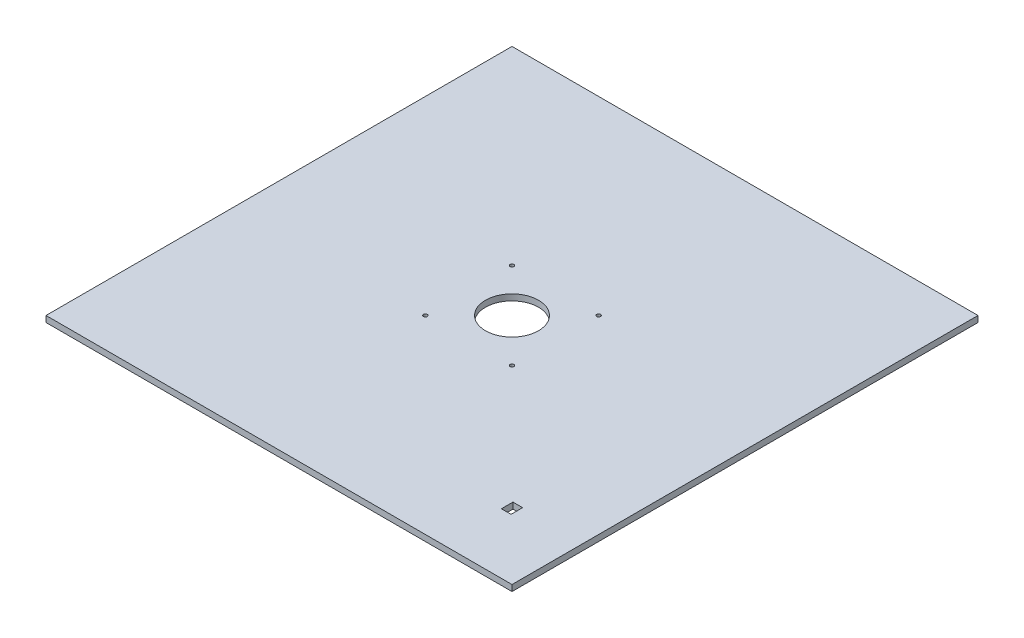
SolidWorks part; units mm, degrees
ref_plane "Front Plane" through (0, 0, 0) normal (0, 0, 1) x (1, 0, 0)
ref_plane "Top Plane" through (0, 0, 0) normal (0, 1, 0) x (1, 0, 0)
ref_plane "Right Plane" through (0, 0, 0) normal (1, 0, 0) x (0, 0, -1)
sketch "Sketch1" plane through (0, 0, 0) normal (0, 1, 0) x (1, 0, 0)
  line L1 (-241.3, -241.3) -> (241.3, -241.3)
  line L2 (-241.3, -241.3) -> (-241.3, 241.3)
  line L3 (-241.3, 241.3) -> (241.3, 241.3)
  line L4 (241.3, -241.3) -> (241.3, 241.3)
  line L5 (-241.3, -241.3) -> (241.3, 241.3) construction
  line L6 (-241.3, 241.3) -> (241.3, -241.3) construction
  point P0 (0, 0)
  dimension "D1" = 482.6
  dimension "D2" = 482.6
extrude "Boss-Extrude1" add sketch "Sketch1" along normal blind 6.35
sketch "Sketch2" plane through (0, 6.35, 0) normal (0, 1, 0) x (1, 0, 0)
  line L1 (-44.8437, -44.8437) -> (44.8437, -44.8437) construction
  line L2 (-44.8437, -44.8437) -> (-44.8437, 44.8437) construction
  line L3 (-44.8437, 44.8437) -> (44.8437, 44.8437) construction
  line L4 (44.8437, -44.8437) -> (44.8437, 44.8437) construction
  line L5 (-44.8437, -44.8437) -> (44.8437, 44.8437) construction
  line L6 (-44.8437, 44.8437) -> (44.8437, -44.8437) construction
  circle A0 centre (-44.8437, 44.8437) radius 1.9844
  circle A1 centre (44.8437, 44.8437) radius 1.9844
  circle A2 centre (-44.8437, -44.8437) radius 1.9844
  circle A3 centre (44.8437, -44.8437) radius 1.9844
  circle A4 centre (0, 0) radius 27.432
  point P0 (0, 0)
  dimension "D3" = 3.9688
  dimension "D4" = 54.864
  dimension "D1" = 89.6874
  dimension "D2" = 89.6874
extrude "Cut-Extrude1" cut sketch "Sketch2" against normal through all and the other way through all
sketch "Sketch3" plane through (0, 6.35, 0) normal (0, 1, 0) x (1, 0, 0)
  line L1 (0, 0) -> (241.3, -241.3) construction
  line L8 (167.8699, -178.8699) -> (177.8699, -178.8699)
  line L9 (167.8699, -178.8699) -> (167.8699, -166.8699)
  line L10 (167.8699, -166.8699) -> (177.8699, -166.8699)
  line L11 (177.8699, -178.8699) -> (177.8699, -166.8699)
  line L12 (167.8699, -178.8699) -> (177.8699, -166.8699) construction
  line L13 (167.8699, -166.8699) -> (177.8699, -178.8699) construction
  point P9 (172.8699, -172.8699)
  point P16 (0, 0)
  point P17 (0, 0)
  dimension "D1" = 244.475
  dimension "D4" = 12
extrude "Cut-Extrude2" cut sketch "Sketch3" against normal through all
